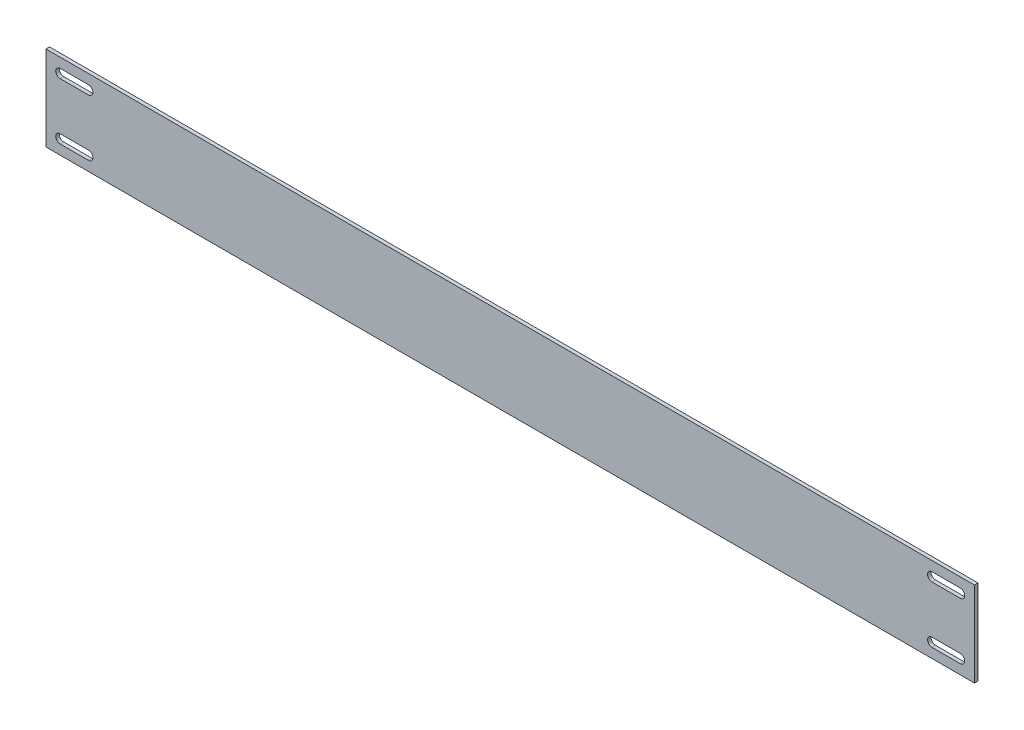
SolidWorks part; units mm, degrees
material "ABS"
ref_plane "Front Plane" through (0, 0, 0) normal (0, 0, 1) x (1, 0, 0)
ref_plane "Top Plane" through (0, 0, 0) normal (0, 1, 0) x (1, 0, 0)
ref_plane "Right Plane" through (0, 0, 0) normal (1, 0, 0) x (0, 0, -1)
sketch "Sketch1" plane through (0, 0, 0) normal (0, 1, 0) x (1, 0, 0)
  line L0 (0, 0) -> (416.56, 0)
  line L1 (416.56, 0) -> (416.56, 1.5875)
  line L2 (416.56, 1.5875) -> (391.16, 1.5875)
  line L5 (0, 0) -> (0, 1.5875)
  line L6 (0, 1.5875) -> (25.4, 1.5875)
  line L8 (25.4, 1.5875) -> (391.16, 1.5875)
  dimension "D1" = 416.56
  dimension "D2" = 25.4
  dimension "D3" = 1.5875
  dimension "D5" = 1.5875
  dimension "D6" = 25.4
extrude "Boss-Extrude1" add sketch "Sketch1" along normal blind 38.1
sketch "Sketch2" plane through (0, 0, -1.5875) normal (0, 0, -1) x (-1, 0, 0)
  line L0 (-208.28, 38.1) -> (-208.28, 0) construction
  line L3 (-25.4, 19.05) -> (0, 19.05) construction
  line L5 (0, 38.1) -> (0, 0) construction
  line L6 (-19.05, 31.75) -> (-6.35, 31.75) construction
  line L7 (-19.05, 33.7344) -> (-6.35, 33.7344)
  line L8 (-19.05, 29.7656) -> (-6.35, 29.7656)
  line L9 (-12.7, 19.05) -> (-12.7, 31.75) construction
  line L10 (-19.05, 6.35) -> (-6.35, 6.35) construction
  line L11 (-19.05, 4.3656) -> (-6.35, 4.3656)
  line L12 (-19.05, 8.3344) -> (-6.35, 8.3344)
  line L13 (-397.51, 6.35) -> (-410.21, 6.35) construction
  line L14 (-397.51, 4.3656) -> (-410.21, 4.3656)
  line L15 (-397.51, 8.3344) -> (-410.21, 8.3344)
  line L16 (-397.51, 31.75) -> (-410.21, 31.75) construction
  line L17 (-397.51, 33.7344) -> (-410.21, 33.7344)
  line L18 (-397.51, 29.7656) -> (-410.21, 29.7656)
  line L19 (0, 38.1) -> (0, 0) construction
  line L20 (-416.56, 38.1) -> (0, 38.1) construction
  line L21 (-416.56, 0) -> (0, 0) construction
  arc A0 (-19.05, 33.7344) -> (-19.05, 29.7656) centre (-19.05, 31.75) ccw
  arc A1 (-6.35, 29.7656) -> (-6.35, 33.7344) centre (-6.35, 31.75) ccw
  arc A2 (-19.05, 4.3656) -> (-19.05, 8.3344) centre (-19.05, 6.35) cw
  arc A3 (-6.35, 8.3344) -> (-6.35, 4.3656) centre (-6.35, 6.35) cw
  arc A4 (-397.51, 4.3656) -> (-397.51, 8.3344) centre (-397.51, 6.35) ccw
  arc A5 (-410.21, 8.3344) -> (-410.21, 4.3656) centre (-410.21, 6.35) ccw
  arc A6 (-397.51, 33.7344) -> (-397.51, 29.7656) centre (-397.51, 31.75) cw
  arc A7 (-410.21, 29.7656) -> (-410.21, 33.7344) centre (-410.21, 31.75) cw
  point P2 (-208.28, 38.1)
  point P14 (-12.7, 31.75)
  point P23 (-12.7, 6.35)
  point P30 (-403.86, 6.35)
  point P37 (-403.86, 31.75)
  dimension "D1" = 12.7
  dimension "D2" = 3.9688
  dimension "D3" = 12.7
  dimension "D4" = 12.7
extrude "Cut-Extrude2" cut sketch "Sketch2" against normal through all contours L8 A1 L7 A0 | A3 L12 A2 L11 | L15 A5 L14 A4 | A7 L18 A6 L17 | L18 A7 L17 A6 region at (12.7, 31.75, -1.5875) region at (12.7, 6.35, -1.5875) region at (403.86, 6.35, -1.5875) region at (403.86, 31.75, -1.5875)
